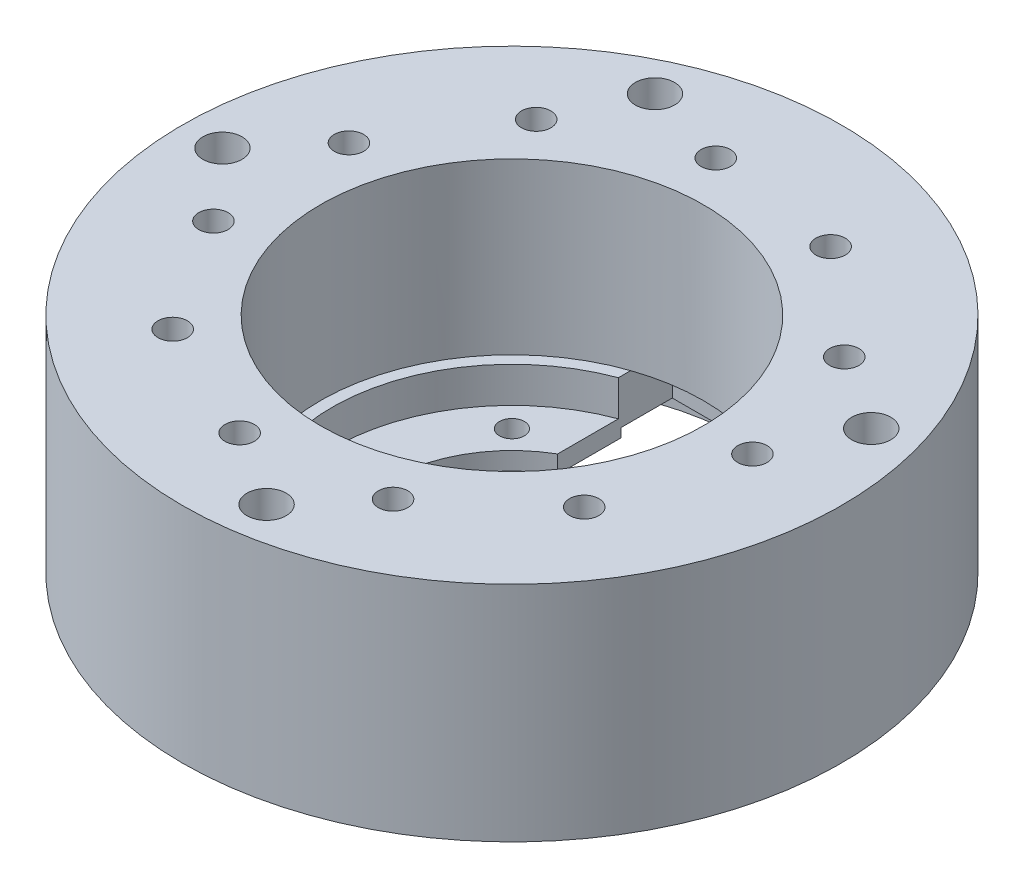
SolidWorks part; units mm, degrees
ref_plane "Front Plane" through (0, 0, 0) normal (0, 0, 1) x (1, 0, 0)
ref_plane "Top Plane" through (0, 0, 0) normal (0, 1, 0) x (1, 0, 0)
ref_plane "Right Plane" through (0, 0, 0) normal (1, 0, 0) x (0, 0, -1)
sketch "Sketch1" plane through (0, 0, 0) normal (0, 1, 0) x (1, 0, 0)
  circle A0 centre (0, 0) radius 37
  dimension "D1" = 74
extrude "Boss-Extrude1" add sketch "Sketch1" along normal blind 25.05
sketch "Sketch2" plane through (0, 25.05, 0) normal (0, 1, 0) x (1, 0, 0)
  circle A0 centre (0, 0) radius 21.5
  dimension "D1" = 43
extrude "Cut-Extrude1" cut sketch "Sketch2" against normal blind 19.05
sketch "Sketch3" plane through (0, 6, 0) normal (0, 1, 0) x (1, 0, 0)
  circle A0 centre (0, 0) radius 20.2
  dimension "D1" = 40.4
extrude "Cut-Extrude2" cut sketch "Sketch3" against normal blind 4
sketch "Sketch4" plane through (0, 2, 0) normal (0, 1, 0) x (1, 0, 0)
  circle A0 centre (0, 0) radius 14
  dimension "D1" = 28
extrude "Cut-Extrude3" cut sketch "Sketch4" against normal through all
sketch "Sketch5" plane through (0, 0, 0) normal (0, 1, 0) x (1, 0, 0)
  line L0 (0, -13.7775) -> (0, 13.7775) construction
  line L1 (-7, 11) -> (7, 11)
  line L2 (-7, 11) -> (-7, 25)
  line L3 (-7, 25) -> (7, 25)
  line L4 (7, 11) -> (7, 25)
  line L5 (-7, 11) -> (7, 25) construction
  line L6 (-7, 25) -> (7, 11) construction
  line L7 (-13.7775, 0) -> (13.7775, 0) construction
  point P0 (0, 18)
  dimension "D1" = 14
  dimension "D2" = 11
  dimension "D3" = 25
extrude "Cut-Extrude4" cut sketch "Sketch5" along normal blind 6
sketch "Sketch6" plane through (0, 0, 0) normal (0, 1, 0) x (1, 0, 0)
  line L0 (-13.7775, 0) -> (13.7775, 0) construction
  line L1 (0, -13.7775) -> (0, 13.7775) construction
  circle A0 centre (12.021, 12.021) radius 1.4
  circle A1 centre (12.021, -12.021) radius 1.4
  circle A2 centre (-12.021, -12.021) radius 1.4
  circle A3 centre (-12.021, 12.021) radius 1.4
  point P15 (0, 0)
  dimension "D1" = 2.8
  dimension "D2" = 12.021
  dimension "D3" = 12.021
  dimension "D4" = 4
extrude "Cut-Extrude5" cut sketch "Sketch6" along normal through all
sketch "Sketch7" plane through (0, 25.05, 0) normal (0, 1, 0) x (1, 0, 0)
  line L0 (-13.7775, 0) -> (13.7775, 0) construction
  line L1 (0, -13.7775) -> (0, 13.7775) construction
  circle A0 centre (27, 0) radius 1.65
  circle A1 centre (22.7138, -14.5973) radius 1.65
  circle A2 centre (11.2162, -24.5601) radius 1.65
  circle A3 centre (-3.8425, -26.7252) radius 1.65
  circle A4 centre (-17.6812, -20.4052) radius 1.65
  circle A5 centre (-25.9063, -7.6068) radius 1.65
  circle A6 centre (-25.9063, 7.6068) radius 1.65
  circle A7 centre (-17.6812, 20.4052) radius 1.65
  circle A8 centre (-3.8425, 26.7252) radius 1.65
  circle A9 centre (11.2162, 24.5601) radius 1.65
  circle A10 centre (22.7138, 14.5973) radius 1.65
  point P28 (0, 0)
  dimension "D1" = 3.3
  dimension "D2" = 27
  dimension "D3" = 11
extrude "Cut-Extrude6" cut sketch "Sketch7" against normal blind 4.75
sketch "Sketch8" plane through (0, 25.05, 0) normal (0, 1, 0) x (1, 0, 0)
  line L0 (0, 0) -> (43.2403, 0) construction
  line L1 (-13.7775, 0) -> (13.7775, 0) construction
  line L2 (0, 0) -> (44.2582, 12.9923) construction
  line L3 (0, 0) -> (-20.2523, 44.3371) construction
  line L4 (0, 0) -> (-46.5124, 0) construction
  line L5 (0, 0) -> (7.8044, -54.2928) construction
  circle A0 centre (31.1841, 9.1543) radius 2.2
  circle A1 centre (-13.5033, 29.562) radius 2.2
  circle A2 centre (-32.5, 0) radius 2.2
  circle A4 centre (4.6242, -32.1693) radius 2.2
  dimension "D5" = 4.4
  dimension "D7" = 4.4
  dimension "D9" = 4.4
  dimension "D11" = 4.4
  dimension "D1" = 16.36
  dimension "D2" = 114.55
  dimension "D3" = 180
  dimension "D4" = 278.18
  dimension "D6" = 32.5
  dimension "D8" = 32.5
  dimension "D10" = 32.5
  dimension "D12" = 32.5
extrude "Cut-Extrude7" cut sketch "Sketch8" against normal blind 5.5
sketch "Sketch9" plane through (0, 0, 0) normal (0, 1, 0) x (1, 0, 0)
  circle A0 centre (0, 0) radius 20.5
  circle A1 centre (0, 0) radius 26
  dimension "D1" = 52
  dimension "D2" = 41
extrude "Cut-Extrude8" cut sketch "Sketch9" along normal blind 1
equation "\"pin_circle_R\" = 27"
equation "\"ecc\" = 1.5"
equation "\"n_pins\" = 11"
equation "\"pin_d\" = 3"
equation "\"out_pin_R\" = 18.5"
equation "\"disc_clr\" = 0.1"
equation "\"seat_6803\" = 26.1"
equation "\"seat_6806\" = 42.1"
equation "\"disc_t\" = 5"
equation "\"out_hole_clr\" = 0.5"
equation "\"boss_17\" = 17.15"
equation "\"rotor_bolt_R\" = 10"
equation "\"m25_clr\" = 2.8"
equation "\"m25_head\" = 5"
equation "\"insert_hole\" = 4.4"
equation "\"csk\" = 0.6"
equation "\"peg_d\" = 3.0"
equation "\"plug_d\" = 8.6"
equation "\"peg_clr\" = 0.3"
equation "\"m3_clr\" = 3.4"
equation "\"m3_head\" = 6.2"
equation "\"pin_press\" = 3.2"
equation "\"pin_slip\" = 3.3"
equation "\"hub_30\" = 30.25"
equation "\"hub_short\" = 0.2"
equation "\"m3_tap\" = 2.8"
equation "\"rear_plate_t\" = 2"
equation "\"motor_ring\" = 40.4"
equation "\"D1@Boss-Extrude1\"=\"rear_plate_t\" + 17.8 + 5.25"
equation "\"D1@Sketch6\"=\"m25_clr\""
equation "\"D1@Sketch7\"=\"pin_slip\""
equation "\"D2@Sketch7\"=\"pin_circle_R\""
equation "\"D5@Sketch8\"=\"insert_hole\""
equation "\"D7@Sketch8\"=\"insert_hole\""
equation "\"D9@Sketch8\"=\"insert_hole\""
equation "\"D11@Sketch8\"=\"insert_hole\""
